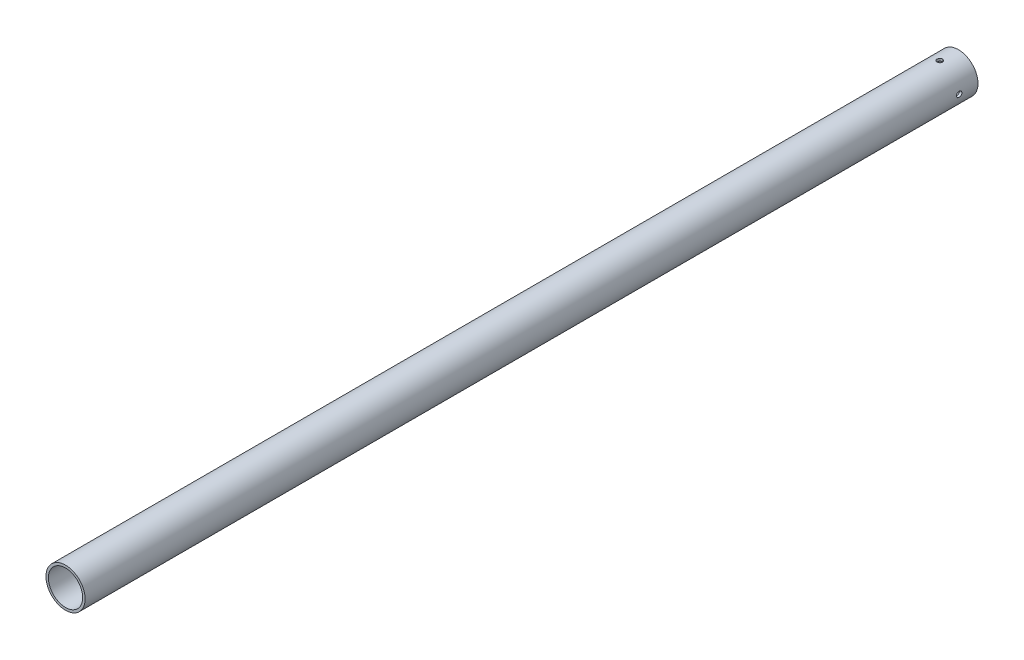
SolidWorks part; units mm, degrees
material "PC High Viscosity"
ref_plane "Front Plane" through (0, 0, 0) normal (0, 0, 1) x (1, 0, 0)
ref_plane "Top Plane" through (0, 0, 0) normal (0, 1, 0) x (1, 0, 0)
ref_plane "Right Plane" through (0, 0, 0) normal (1, 0, 0) x (0, 0, -1)
sketch "Sketch2" plane through (0, 0, 0) normal (0, 0, 1) x (1, 0, 0)
  circle A0 centre (0, 0) radius 11.1125
  circle A1 centre (0, 0) radius 12.7
  dimension "D1" = 25.4
  dimension "D2" = 1.5875
extrude "Boss-Extrude1" add sketch "Sketch2" along normal mid plane 579.1873
sketch "Sketch3" plane through (0, 0, 0) normal (0, 1, 0) x (1, 0, 0)
  line L0 (12.7, 289.5936) -> (-12.7, 289.5936) construction
  circle A0 centre (0, 277.4016) radius 1.7526
  dimension "D1" = 3.5052
  dimension "D2" = 12.192
extrude "Cut-Extrude1" cut sketch "Sketch3" against normal through all both and the other way through all
sketch "Sketch5" plane through (0, 0, 0) normal (1, 0, 0) x (0, 0, -1)
  line L0 (289.5936, -12.7) -> (289.5936, 12.7) construction
  circle A0 centre (277.4016, 0) radius 1.7526
  dimension "D1" = 3.5052
  dimension "D2" = 12.192
extrude "Cut-Extrude2" cut sketch "Sketch5" against normal through all both and the other way through all
